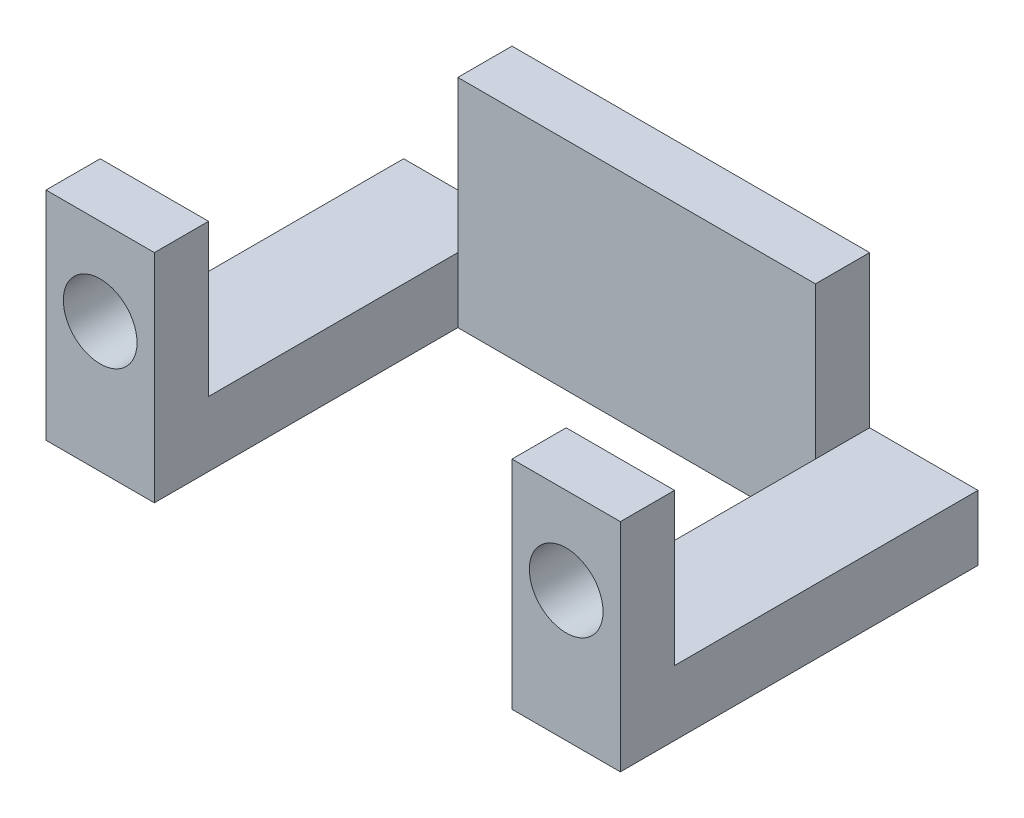
SolidWorks part; units mm, degrees
ref_plane "Front Plane" through (0, 0, 0) normal (0, 0, 1) x (1, 0, 0)
ref_plane "Top Plane" through (0, 0, 0) normal (0, 1, 0) x (1, 0, 0)
ref_plane "Right Plane" through (0, 0, 0) normal (1, 0, 0) x (0, 0, -1)
sketch "Sketch1" plane through (0, 0, 0) normal (0, 0, 1) x (1, 0, 0)
  line L0 (-661.7423, -346.4261) -> (-661.7423, -366.4261)
  line L1 (-671.7423, -346.4261) -> (-618.7423, -346.4261)
  line L2 (-671.7423, -346.4261) -> (-671.7423, -366.4261)
  line L3 (-671.7423, -366.4261) -> (-618.7423, -366.4261)
  line L4 (-618.7423, -346.4261) -> (-618.7423, -366.4261)
  line L5 (-628.7423, -346.4261) -> (-628.7423, -366.4261)
  line L6 (-671.7423, -360.4261) -> (-661.7423, -360.4261)
  line L7 (-628.7423, -360.4261) -> (-618.7423, -360.4261)
  circle A0 centre (-666.7423, -354.4261) radius 3.4
  circle A1 centre (-623.7423, -354.4261) radius 3.4
  dimension "D5" = 5
  dimension "D1" = 53
  dimension "D2" = 20
  dimension "D3" = 10
  dimension "D4" = 10
  dimension "D6" = 12
  dimension "D7" = 5
  dimension "D8" = 12
  dimension "D9" = 6
  dimension "D10" = 6
extrude "Boss-Extrude1" add sketch "Sketch1" along normal blind 5 contours L5 L1 L0 L3 region at (-645.2423, -356.4261, 0)
extrude "Boss-Extrude2" add sketch "Sketch1<7>" along normal blind 33 contours L7 L5 L3 L4 | L6 L2 L3 L0 region at (-666.7423, -363.4261, 0) region at (-623.7423, -363.4261, 0)
sketch "Sketch1<7>" plane through (0, 0, 0) normal (0, 0, 1) x (1, 0, 0) same geometry as "Sketch1"
extrude "Boss-Extrude3" add sketch "Sketch1<9>" along direction (0, 0, 1) on the side against the normal blind 5 from offset 33 contours L2 L6 L0 L1 A0 | L5 L7 L4 L1 A1 region at (-661.9143, -353.4261, 0) region at (-623.7423, -346.5981, 0)
sketch "Sketch1<9>" plane through (0, 0, 0) normal (0, 0, 1) x (1, 0, 0) same geometry as "Sketch1"
